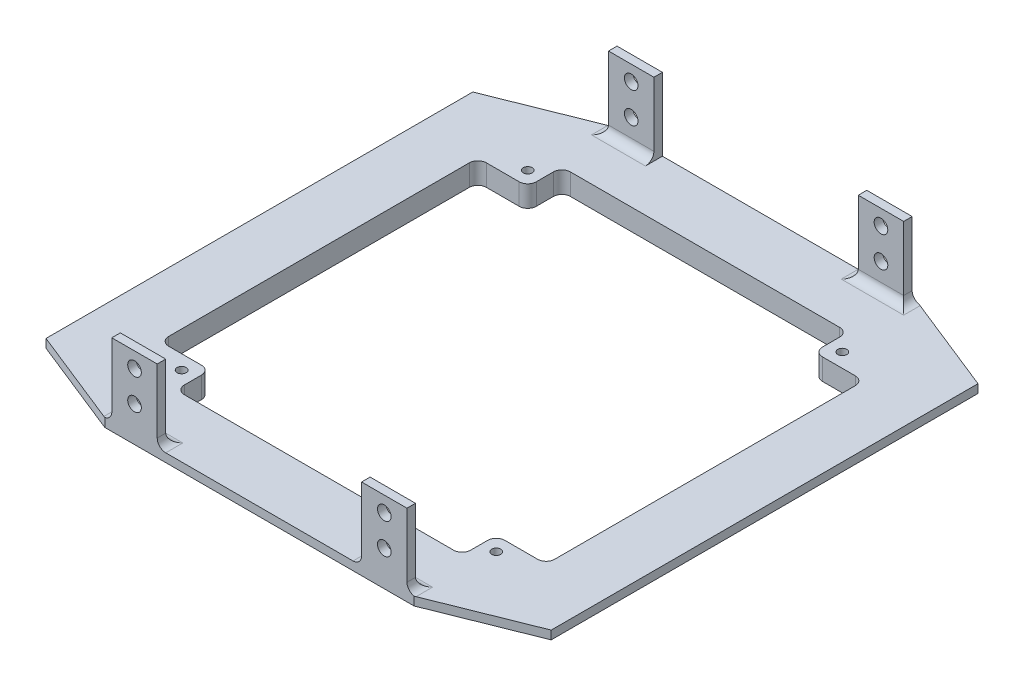
SolidWorks part; units mm, degrees
material "6061-T6 (SS)"
ref_plane "Front Plane" through (0, 0, 0) normal (0, 0, 1) x (1, 0, 0)
ref_plane "Top Plane" through (0, 0, 0) normal (0, 1, 0) x (1, 0, 0)
ref_plane "Right Plane" through (0, 0, 0) normal (1, 0, 0) x (0, 0, -1)
sketch "Sketch1" plane through (0, 0, 0) normal (0, 1, 0) x (1, 0, 0)
  line L5 (-35.5, 0) -> (0, 0) construction
  line L6 (-25.5, -35.5) -> (25.5, -35.5)
  line L10 (-35.5, -31.5) -> (-35.5, 31.5)
  line L11 (-25.5, 35.5) -> (25.5, 35.5)
  line L12 (35.5, -31.5) -> (35.5, 31.5)
  line L13 (0, 0) -> (0, 35.5) construction
  line L14 (25.5, -35.5) -> (35.5, -31.5)
  line L15 (25.5, 35.5) -> (35.5, 31.5)
  line L16 (-25.5, -35.5) -> (-35.5, -31.5)
  line L17 (-25.5, 35.5) -> (-35.5, 31.5)
  point P0 (0, 0)
  point P4 (35.5, -35.5)
  dimension "D3" = 4
  dimension "D2" = 10
  dimension "D4" = 71
extrude "Boss-Extrude1" add sketch "Sketch1" along normal mid plane 4.5
sketch "Sketch2" plane through (0, 2.25, 0) normal (0, 1, 0) x (1, 0, 0)
  line L16 (27.2332, -44.5) -> (44.5, -37.5933)
  line L17 (44.5, -37.5933) -> (44.5, 37.5933)
  line L18 (44.5, 37.5933) -> (27.2332, 44.5)
  line L19 (27.2332, 44.5) -> (-27.2332, 44.5)
  line L20 (-27.2332, 44.5) -> (-44.5, 37.5933)
  line L21 (-44.5, 37.5933) -> (-44.5, -37.5933)
  line L22 (-44.5, -37.5933) -> (-27.2332, -44.5)
  line L23 (-27.2332, -44.5) -> (27.2332, -44.5)
  line L24 (27.2332, -44.5) -> (44.5, -37.5933)
  line L25 (44.5, -37.5933) -> (44.5, 37.5933)
  line L26 (44.5, 37.5933) -> (27.2332, 44.5)
  line L27 (27.2332, 44.5) -> (-27.2332, 44.5)
  line L28 (-27.2332, 44.5) -> (-44.5, 37.5933)
  line L29 (-44.5, 37.5933) -> (-44.5, -37.5933)
  line L30 (-44.5, -37.5933) -> (-27.2332, -44.5)
  line L31 (-27.2332, -44.5) -> (27.2332, -44.5)
  dimension "D1" = 9
extrude "Boss-Extrude2" add sketch "Sketch2" along normal blind 1.5
mirror "Mirror1" about plane through (0, 0, 0) normal (0, 1, 0) of "Boss-Extrude2"
sketch "Sketch3" plane through (0, 0, 0) normal (0, 1, 0) x (1, 0, 0)
  line L16 (-25.2111, -34) -> (25.2111, -34)
  line L17 (25.2111, -34) -> (34, -30.4845)
  line L18 (34, -30.4845) -> (34, 30.4845)
  line L19 (34, 30.4845) -> (25.2111, 34)
  line L20 (25.2111, 34) -> (-25.2111, 34)
  line L21 (-25.2111, 34) -> (-34, 30.4845)
  line L22 (-34, 30.4845) -> (-34, -30.4845)
  line L23 (-34, -30.4845) -> (-25.2111, -34)
  line L24 (-25.2111, -34) -> (25.2111, -34)
  line L25 (25.2111, -34) -> (34, -30.4845)
  line L26 (34, -30.4845) -> (34, 30.4845)
  line L27 (34, 30.4845) -> (25.2111, 34)
  line L28 (25.2111, 34) -> (-25.2111, 34)
  line L29 (-25.2111, 34) -> (-34, 30.4845)
  line L30 (-34, 30.4845) -> (-34, -30.4845)
  line L31 (-34, -30.4845) -> (-25.2111, -34)
  dimension "D1" = 10.5
extrude "Cut-Extrude1" cut sketch "Sketch3" against normal through all both and the other way through all
sketch "Sketch5" plane through (0, 0, 0) normal (0, 0, 1) x (1, 0, 0)
  line L0 (0, 0) -> (0, 28.4264) construction
  line L1 (-27.2332, 3.75) -> (27.2332, 3.75) construction
  line L2 (-26, 3.75) -> (-18, 3.75)
  line L3 (-26, 3.75) -> (-26, 16.55)
  line L4 (-26, 16.55) -> (-18, 16.55)
  line L5 (-18, 3.75) -> (-18, 16.55)
  line L6 (-22, 16.55) -> (-22, 9.7096) construction
  line L7 (18, 3.75) -> (18, 16.55)
  line L8 (26, 16.55) -> (18, 16.55)
  line L9 (26, 3.75) -> (26, 16.55)
  line L10 (26, 3.75) -> (18, 3.75)
  dimension "D1" = 22
  dimension "D3" = 12.8
  dimension "D2" = 8
extrude "Boss-Extrude3" add sketch "Sketch5" against normal blind 1.5 from surface starting at face at (0, 3, 44.5)
extrude "Boss-Extrude4" add sketch "Sketch5<2>" along normal blind 1.5 from surface starting at face at (0, 3, -44.5)
sketch "Sketch5<2>" plane through (0, 0, 0) normal (0, 0, 1) x (1, 0, 0) same geometry as "Sketch5"
sketch "Sketch6" plane through (0, 0, 0) normal (0, 0, 1) x (1, 0, 0)
  line L0 (-22, 16.55) -> (-22, 13.85) construction
  line L1 (-18, 16.55) -> (-26, 16.55) construction
  line L2 (0, 0) -> (0, 25.5714) construction
  line L3 (-22, 13.85) -> (-22, 8.45) construction
  circle A0 centre (-22, 13.85) radius 1.2
  circle A1 centre (22, 13.85) radius 1.2
  circle A2 centre (-22, 8.45) radius 1.2
  circle A3 centre (22, 8.45) radius 1.2
  dimension "D1" = 2.4
  dimension "D2" = 2.7
  dimension "D3" = 5.4
extrude "Cut-Extrude3" cut sketch "Sketch6" against normal through all both and the other way through all
fillet "Fillet1" radius 1.5 35 edges at (35.5, 0, 31.5) (25.5, 0, 35.5) (0, 2.25, -35.5) (0, -2.25, -35.5) (35.5, 2.25, 0) (35.5, -2.25, 0) (-35.5, 2.25, 0) (-35.5, -2.25, 0) (0, 2.25, 35.5) (0, -2.25, 35.5) (-25.5, 0, -35.5) (-30.5, 2.25, -33.5) (-35.5, 0, -31.5) (-30.5, -2.25, -33.5) (35.5, 0, -31.5) (30.5, 2.25, -33.5) (25.5, 0, -35.5) (30.5, -2.25, -33.5) (30.5, 2.25, 33.5) (30.5, -2.25, 33.5) (-35.5, 0, 31.5) (-30.5, 2.25, 33.5) (-25.5, 0, 35.5) (-30.5, -2.25, 33.5) (-22, 3.75, -43) (22, 3.75, -43) (-22, 3.75, 43) (22, 3.75, 43) (26, 3.75, 43.75) (-18, 3.75, 43.75) (18, 3.75, 43.75) (-26, 3.75, 43.75) (18, 3.75, -43.75) (26, 3.75, -43.75) (-26, 3.75, -43.75)
sketch "Sketch7" plane through (0, 0, 0) normal (0, 1, 0) x (1, 0, 0)
  line L0 (44.5, -37.5933) -> (44.5, 37.5933) construction
  line L1 (-44.5, 44.5) -> (44.5, 44.5)
  line L2 (-44.5, 44.5) -> (-44.5, -44.5)
  line L3 (-44.5, -44.5) -> (44.5, -44.5)
  line L4 (44.5, 44.5) -> (44.5, -44.5)
  line L5 (-44.5, 44.5) -> (44.5, -44.5) construction
  line L6 (-44.5, -44.5) -> (44.5, 44.5) construction
  line L7 (-16.5, -44.5) -> (16.5, -44.5) construction
  point P1 (0, 0)
extrude "Cut-Extrude4" cut sketch "Sketch7" against normal through all
sketch "Sketch8" plane through (0, 0, 0) normal (0, 1, 0) x (1, 0, 0)
  line L0 (-25.2111, -34) -> (-34, -30.4845)
  line L1 (-34, -30.4845) -> (-34, -27.9845)
  line L2 (-34, 30.4845) -> (-34, -30.4845) construction
  line L3 (-34, -27.9845) -> (-25.2111, -27.9845)
  line L4 (-25.2111, -27.9845) -> (-25.2111, -34)
  line L5 (0, 44.5) -> (0, -44.5) construction
  line L6 (-16.5, -44.5) -> (16.5, -44.5) construction
  line L7 (-44.5, 0) -> (44.5, 0) construction
  line L8 (44.5, -37.5933) -> (44.5, 37.5933) construction
  line L9 (-34, -30.4845) -> (-25.2111, -30.4845) construction
  line L10 (34, -30.4845) -> (25.2111, -30.4845) construction
  line L11 (25.2111, -27.9845) -> (25.2111, -34)
  line L12 (34, -27.9845) -> (25.2111, -27.9845)
  line L13 (34, -30.4845) -> (34, -27.9845)
  line L14 (25.2111, -34) -> (34, -30.4845)
  line L15 (34, 30.4845) -> (25.2111, 30.4845) construction
  line L16 (-34, 30.4845) -> (-25.2111, 30.4845) construction
  line L17 (25.2111, 34) -> (34, 30.4845)
  line L18 (34, 30.4845) -> (34, 27.9845)
  line L19 (34, 27.9845) -> (25.2111, 27.9845)
  line L20 (25.2111, 27.9845) -> (25.2111, 34)
  line L21 (-25.2111, 27.9845) -> (-25.2111, 34)
  line L22 (-34, 27.9845) -> (-25.2111, 27.9845)
  line L23 (-34, 30.4845) -> (-34, 27.9845)
  line L24 (-25.2111, 34) -> (-34, 30.4845)
  point P4 (-27.7111, -30.4845)
  point P14 (0, 0)
  point P20 (0, 0)
  point P25 (27.7111, -30.4845)
  point P34 (-27.7111, 30.4845)
  point P35 (27.7111, 30.4845)
  dimension "D2" = 2.5
  dimension "D1" = 2.5
extrude "Boss-Extrude5" add sketch "Sketch8" along normal up to surface (3.75 mm away) up to face at (0, 3.75, 0)
fillet "Fillet2" radius 1.5 12 edges at (-34, 1.875, 27.9845) (-25.2111, 1.875, 34) (25.2111, 1.875, 34) (34, 1.875, 27.9845) (25.2111, 1.875, -34) (34, 1.875, -27.9845) (-34, 1.875, -27.9845) (-25.2111, 1.875, -34) (25.2111, 1.875, -27.9845) (-25.2111, 1.875, -27.9845) (-25.2111, 1.875, 27.9845) (25.2111, 1.875, 27.9845)
hole_wizard "M2x0.4 Tapped Hole1" positions "Sketch11" profile "Sketch12" tap size "M2x0.4" standard "ANSI Metric" end condition through all
sketch "Sketch11" plane through (0, 3.75, 0) normal (0, 1, 0) x (1, 0, 0)
  point P0 (-27.7111, 30.4845)
  point P3 (27.7111, 30.4845)
  point P6 (27.7111, -30.4845)
  point P9 (-27.7111, -30.4845)
sketch "Sketch12" plane through (-27.7111, 3.75, -30.4845) normal (1, 0, 0) x (0, 0, 1)
  line L0 (0, 0) -> (0, 3.75)
  line L1 (0, 3.75) -> (0.8, 3.75)
  line L2 (0.8, 3.75) -> (0.8, 0)
  line L5 (0.8, 0) -> (0, 0)
  line L11 (0, -6.35) -> (0, 107.95) construction
  dimension "Thru Tap Drill Dia." = 1.6
  dimension "Thru Tap Drill Depth" = 3.75
cosmetic thread "Hole Thread1" parameters "D2"=2
cosmetic thread "Hole Thread2" parameters "D2"=2
cosmetic thread "Hole Thread3" parameters "D2"=2
cosmetic thread "Hole Thread4" parameters "D2"=2
